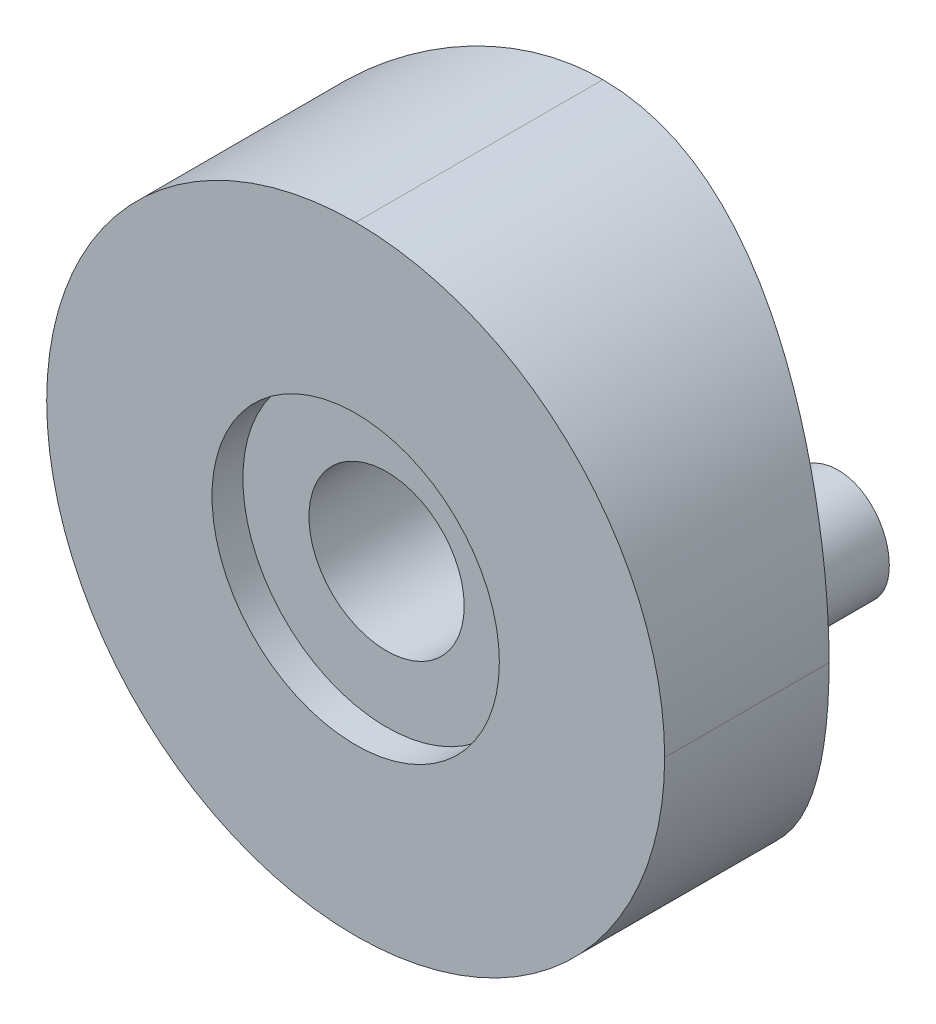
SolidWorks part; units mm, degrees
ref_plane "Front Plane" through (0, 0, 0) normal (0, 0, 1) x (1, 0, 0)
ref_plane "Top Plane" through (0, 0, 0) normal (0, 1, 0) x (1, 0, 0)
ref_plane "Right Plane" through (0, 0, 0) normal (1, 0, 0) x (0, 0, -1)
sketch "Sketch3" plane through (0, 0, 0) normal (1, 0, 0) x (0, 0, -1)
  line L0 (0, 20) -> (-8, 20)
  line L1 (-8, 20) -> (-8, 0)
  line L2 (-8, 0) -> (0, 0)
  arc A0 (0, 0) -> (0, 20) centre (17.3205, 10) cw
  dimension "D1" = 20
  dimension "D2" = 20
  dimension "D3" = 8
extrude "Boss-Extrude2" add sketch "Sketch3" along normal blind 20
fillet "Fillet1" radius 10 4 edges at (20, 0, 4) (0, 0, 4) (20, 20, 4) (0, 20, 4)
sketch "Sketch4" plane through (0, 0, 8) normal (0, 0, 1) x (1, 0, 0)
  circle A0 centre (10, 10) radius 2.5125
  arc A1 (10, 20) -> (0, 10) centre (10, 10) ccw construction
  dimension "D1" = 5.025
extrude "Cut-Extrude2" cut sketch "Sketch4" against normal up to surface (5.3205 mm away)
sketch "Sketch6" plane through (0, 0, 8) normal (0, 0, 1) x (1, 0, 0)
  line L0 (10, 12.5125) -> (10, 7.4875) construction
  circle A0 centre (3.5, 10) radius 1.75
  circle A1 centre (10, 10) radius 2.5125 construction
  circle A2 centre (10, 10) radius 2.5125 construction
  circle A3 centre (16.5, 10) radius 1.75
  dimension "D2" = 3.5
  dimension "D1" = 6.5
extrude "Boss-Extrude3" add sketch "Sketch6" against normal offset from surface (9.0205 mm away) 3.7
sketch "Sketch7" plane through (0, 0, 8) normal (0, 0, 1) x (1, 0, 0)
  circle A2 centre (10, 10) radius 4.65
  circle A3 centre (10, 10) radius 2.5125 construction
  dimension "D1" = 9.3
extrude "Cut-Extrude4" cut sketch "Sketch7" against normal blind 1
